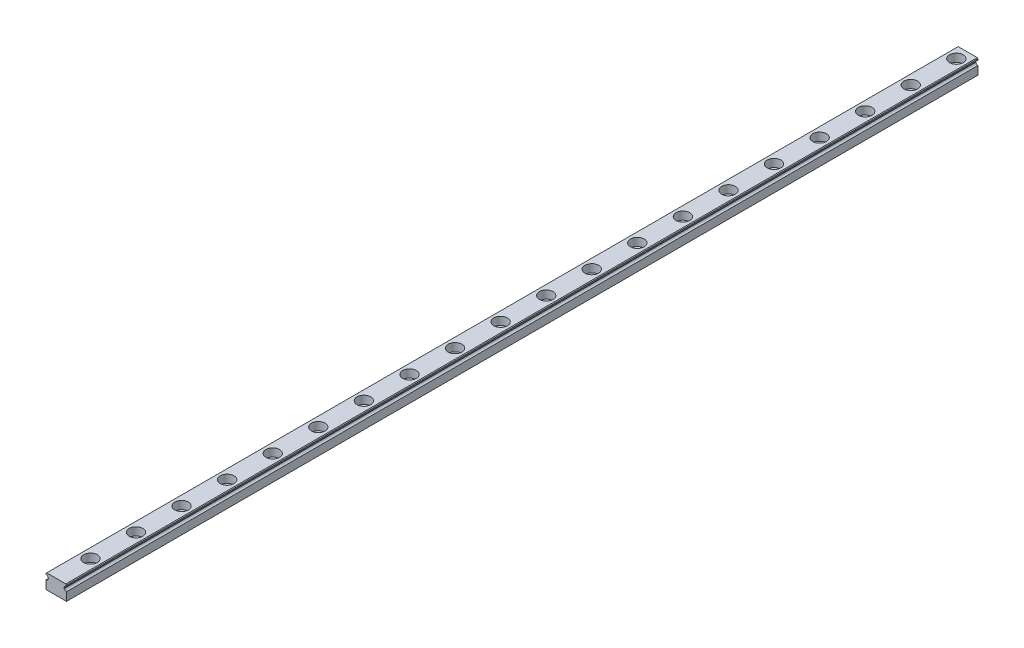
SolidWorks part; units mm, degrees
ref_plane "Спереди" through (0, 0, 0) normal (0, 0, 1) x (1, 0, 0)
ref_plane "Сверху" through (0, 0, 0) normal (0, 1, 0) x (1, 0, 0)
ref_plane "Справа" through (0, 0, 0) normal (1, 0, 0) x (0, 0, -1)
other "Configuration Table"
sketch "Sketch1" plane through (0, 0, 0) normal (0, 0, 1) x (1, 0, 0)
  line L0 (0, 0) -> (0, 5.7299) construction
  line L1 (-4.5, -3.25) -> (4.5, -3.25)
  line L2 (-4.5, -3.25) -> (-4.5, 0.45)
  line L3 (-4.5, 3.25) -> (4.5, 3.25)
  line L4 (4.5, -3.25) -> (4.5, 0.45)
  line L5 (-4.5, -3.25) -> (4.5, 3.25) construction
  line L6 (-4.5, 3.25) -> (4.5, -3.25) construction
  line L7 (-4.5, 2.45) -> (-4.5, 3.25)
  line L8 (-3.5318, 1.2) -> (-3.4, 1.2)
  line L9 (3.5318, 1.2) -> (3.4, 1.2)
  line L10 (-3.5318, 1.7) -> (-3.4, 1.7)
  line L11 (-3.4, 1.2) -> (-3.4, 1.7)
  line L12 (3.4, 1.2) -> (3.4, 1.7)
  line L13 (3.5318, 1.7) -> (3.4, 1.7)
  line L14 (4.5, 2.45) -> (4.5, 3.25)
  line L15 (-3.4, 1.45) -> (-4.5, 1.45) construction
  arc A0 (-3.5318, 1.7) -> (-4.5, 2.45) centre (-4.5, 1.45) ccw
  arc A1 (-4.5, 0.45) -> (-3.5318, 1.2) centre (-4.5, 1.45) ccw
  arc A2 (4.5, 0.45) -> (3.5318, 1.2) centre (4.5, 1.45) cw
  arc A3 (3.5318, 1.7) -> (4.5, 2.45) centre (4.5, 1.45) cw
  point P0 (0, 0)
  dimension "D3" = 1
  dimension "D1" = 9
  dimension "D2" = 6.5
  dimension "D4" = 2.05
  dimension "D5" = 6.8
  dimension "D6" = 0.5
extrude "Extrude1" add sketch "Sketch1" along normal blind 400
sketch "Sketch2" plane through (0, 3.25, 0) normal (0, 1, 0) x (1, 0, 0)
  line L0 (4.5, 0) -> (-4.5, 0) construction
  circle A0 centre (0, -5) radius 1.75
  circle A1 centre (0, -5) radius 3
  dimension "D1" = 3.5
  dimension "D2" = 6
  dimension "D3" = 5
extrude "Extrude2" cut sketch "Sketch2" against normal blind 3.5 contours A1
extrude "Extrude3" cut sketch "Sketch" against normal through all contours A0
sketch "Sketch" plane through (0, 3.25, 0) normal (0, 1, 0) x (1, 0, 0) same geometry as "Sketch2"
pattern_linear "LPattern1" count 40 spacing 20 along (0, 0, 1) of "Extrude2", "Extrude3"
chamfer "Chamfer1" distance 0.3 angle 45 2 edges at (4.5, 3.25, 200) (-4.5, 3.25, 200)
